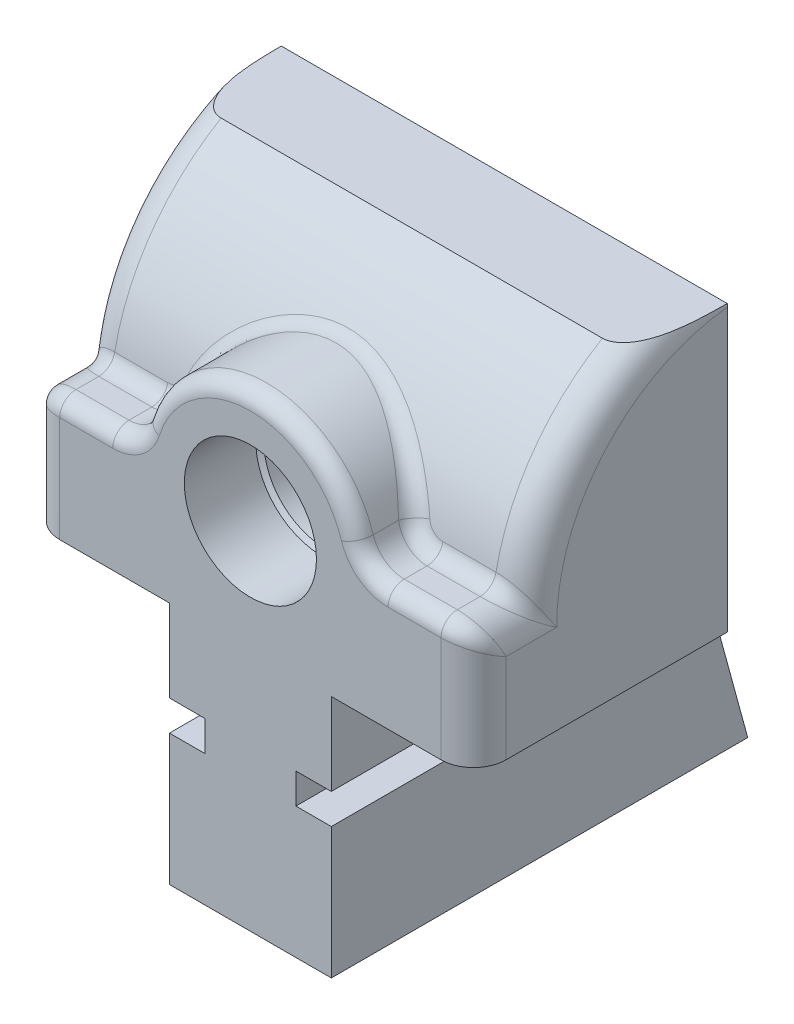
SolidWorks part; units mm, degrees
ref_plane "Front Plane" through (0, 0, 0) normal (0, 0, 1) x (1, 0, 0)
ref_plane "Top Plane" through (0, 0, 0) normal (0, 1, 0) x (1, 0, 0)
ref_plane "Right Plane" through (0, 0, 0) normal (1, 0, 0) x (0, 0, -1)
sketch "Sketch1" plane through (0, 0, 0) normal (0, 0, 1) x (1, 0, 0)
  line L0 (0, 66.9524) -> (0, 0) construction
  line L1 (12.6492, 0.0311) -> (12.6492, 38.1311)
  line L2 (12.6492, 38.1311) -> (34.8742, 38.1311)
  line L3 (34.8742, 38.1311) -> (34.8742, 57.1811)
  line L4 (-34.8742, 38.1311) -> (-34.8742, 57.1811)
  line L5 (-12.6492, 38.1311) -> (-34.8742, 38.1311)
  line L6 (-12.6492, 0.0311) -> (-12.6492, 38.1311)
  line L7 (-34.8742, 57.1811) -> (34.8742, 57.1811)
  line L8 (-12.6492, 0.0311) -> (12.6492, 0.0311)
  dimension "D1" = 38.1
  dimension "D2" = 22.225
  dimension "D3" = 19.05
  dimension "D4" = 25.2984
extrude "Boss-Extrude1" add sketch "Sketch1" along normal blind 65.0748
sketch "Sketch2" plane through (-34.8742, 0, 0) normal (-1, 0, 0) x (0, 0, 1)
  line L0 (56.8255, 57.1811) -> (25.4, 57.1811)
  line L1 (65.0748, 57.1811) -> (0, 57.1811) construction
  line L2 (25.4, 57.1811) -> (25.4, 82.5811)
  line L3 (25.4, 82.5811) -> (39.853, 82.5811)
  line L4 (65.0748, 57.1811) -> (65.0748, 38.1311) construction
  line L5 (65.0748, 38.1311) -> (0, 38.1311) construction
  arc A0 (39.853, 82.5811) -> (56.8255, 57.1811) centre (22.225, 52.4313) cw
  dimension "D2" = 34.925
  dimension "D4" = 3.175
  dimension "D1" = 39.6748
  dimension "D3" = 44.45
  dimension "D5" = 30.1498
extrude "Boss-Extrude2" add sketch "Sketch2" against normal up to surface (69.7484 mm away) up to face at (34.8742, 47.6561, 32.5374)
sketch "Sketch3" plane through (-34.8742, 0, 0) normal (-1, 0, 0) x (0, 0, 1)
  line L0 (25.4, 57.1811) -> (25.4, 34.9561)
  line L1 (25.4, 34.9561) -> (9.525, 34.9561)
  line L2 (9.525, 34.9561) -> (0, 0.0311)
  line L3 (0, 38.1311) -> (0, 0.0311) construction
  line L4 (65.0748, 0.0311) -> (0, 0.0311) construction
  dimension "D1" = 9.525
  dimension "D2" = 34.925
extrude "Cut-Extrude2" cut sketch "Sketch3" against normal through all and the other way through all flip side to cut
sketch "Sketch4" plane through (0, 0, 65.0748) normal (0, 0, 1) x (1, 0, 0)
  line L0 (0, 0) -> (0, 55.5498) construction
  line L1 (-17.4498, 55.5498) -> (17.4498, 55.5498)
  arc A0 (17.4498, 55.5498) -> (-17.4498, 55.5498) centre (0, 55.5498) ccw
  dimension "D2" = 34.8996
  dimension "D1" = 55.5498
extrude "Boss-Extrude3" add sketch "Sketch4" against normal up to surface (8.0643 mm away) up to face at (0, 70.8582, 49.8014)
sketch "Sketch5" plane through (0, 0, 65.0748) normal (0, 0, 1) x (1, 0, 0)
  circle A1 centre (0, 55.5498) radius 9.525
  dimension "D1" = 19.05
extrude "Cut-Extrude3" cut sketch "Sketch5" against normal blind 30.1498
hole_wizard "1-1/8-7 Tapped Hole1" positions "Sketch6" profile "Sketch7" tap size "1-1/8-7" standard "ANSI Inch"
sketch "Sketch6" plane through (0, 0, 65.0748) normal (0, 0, 1) x (1, 0, 0)
  point P0 (0, 55.5498)
sketch "Sketch7" plane through (0, 55.5498, 65.0748) normal (1, 0, 0) x (0, -1, 0)
  line L0 (0, 0) -> (0, 17.3799)
  line L1 (0, 17.3799) -> (10.3251, 11.176)
  line L2 (10.3251, 11.176) -> (10.3251, 0)
  line L5 (10.3251, 0) -> (0, 0)
  line L10 (0, 17.3799) -> (-10.3251, 11.176) construction
  line L11 (0, -6.35) -> (0, 107.95) construction
  dimension "Tap Drill Dia." = 20.6502
  dimension "Tap Drill Depth" = 11.176
  dimension "Drill Angle" = 118
cosmetic thread "Hole Thread1" parameters "D1"=57.15, "D2"=28.575
sketch "Sketch8" plane through (0, 0, 65.0748) normal (0, 0, 1) x (1, 0, 0)
  line L0 (0, 0) -> (0, 50.9626) construction
  line L1 (12.6492, 0.0311) -> (12.6492, 38.1311) construction
  line L2 (12.6492, 25.2787) -> (7.112, 25.2787)
  line L3 (12.6492, 25.2787) -> (12.6492, 20.5289)
  line L4 (12.6492, 20.5289) -> (7.112, 20.5289)
  line L5 (7.112, 25.2787) -> (7.112, 20.5289)
  line L6 (12.6492, 38.1311) -> (34.8742, 38.1311) construction
  dimension "D1" = 5.5372
  dimension "D2" = 4.7498
  dimension "D3" = 12.8524
extrude "Cut-Extrude4" cut sketch "Sketch8" against normal through all
mirror "Mirror1" about plane through (0, 0, 0) normal (1, 0, 0) of "Cut-Extrude4"
hole_wizard "1/4-20 Tapped Hole1" positions "Sketch9" profile "Sketch10" tap size "1/4-20" standard "ANSI Inch"
sketch "Sketch9" plane through (0, 0, 25.4) normal (0, 0, -1) x (-1, 0, 0)
  line L0 (0, 82.5811) -> (0, 25.8742) construction
  line L1 (-34.8742, 82.5811) -> (34.8742, 82.5811) construction
  line L2 (34.8742, 38.1311) -> (12.6492, 38.1311) construction
  point P0 (-19.05, 63.5311)
  point P8 (19.05, 63.5311)
  dimension "D1" = 38.1
  dimension "D2" = 25.4
sketch "Sketch10" plane through (19.05, 63.5311, 25.4) normal (1, 0, 0) x (0, 1, 0)
  line L0 (0, 0) -> (0, 17.5358)
  line L1 (0, 17.5358) -> (2.5527, 16.002)
  line L2 (2.5527, 16.002) -> (2.5527, 0)
  line L5 (2.5527, 0) -> (0, 0)
  line L10 (0, 17.5358) -> (-2.5527, 16.002) construction
  line L11 (0, -6.35) -> (0, 107.95) construction
  dimension "Tap Drill Dia." = 5.1054
  dimension "Tap Drill Depth" = 16.002
  dimension "Drill Angle" = 118
cosmetic thread "Hole Thread2" parameters "D1"=12.7, "D2"=6.35
cosmetic thread "Hole Thread3" parameters "D1"=12.7, "D2"=6.35
fillet "Fillet1" radius 5.08 8 edges at (34.8742, 71.8353, 51.2637) (34.8742, 57.1811, 60.9502) (34.8742, 47.6561, 65.0748) (-34.8742, 71.8353, 51.2637) (-34.8742, 47.6561, 65.0748) (-34.8742, 57.1811, 60.9502) (17.3734, 57.1811, 60.9502) (-17.3734, 57.1811, 60.9502)
fillet "Fillet2" radius 2.54 14 edges at (33.3863, 55.6932, 63.5869) (25.6506, 57.1811, 65.0748) (18.4971, 58.1688, 65.0748) (0, 72.9996, 65.0748) (-18.4971, 58.1688, 65.0748) (-33.3863, 55.6932, 63.5869) (32.3808, 56.4733, 56.2026) (25.6506, 57.1811, 56.8255) (18.656, 58.0566, 56.694) (-2.1278, 72.8694, 50.5453) (-18.3625, 58.2713, 56.6583) (-32.3808, 56.4733, 56.2026) (-25.6506, 57.1811, 65.0748) (-25.6506, 57.1811, 56.8255)
hole_wizard "#25 (0.1495) Diameter Hole1" positions "Sketch11" profile "Sketch12" hole size "#25" standard "ANSI Inch"
sketch "Sketch11" plane through (0, 0.0311, 0) normal (0, -1, 0) x (-1, 0, 0)
  line L0 (0, 0) -> (0, -65.0748) construction
  line L1 (12.6492, -65.0748) -> (-12.6492, -65.0748) construction
  point P0 (-7.9375, -34.925)
  dimension "D1" = 30.1498
  dimension "D2" = 7.9375
sketch "Sketch12" plane through (7.9375, 0.0311, 34.925) normal (1, 0, 0) x (0, 0, -1)
  line L0 (0, 0) -> (0, 28.1156)
  line L1 (0, 28.1156) -> (1.8986, 26.9748)
  line L2 (1.8986, 26.9748) -> (1.8986, 0)
  line L5 (1.8986, 0) -> (0, 0)
  line L10 (0, 28.1156) -> (-1.8987, 26.9748) construction
  line L11 (0, -6.35) -> (0, 107.95) construction
  dimension "Hole Dia." = 3.7973
  dimension "Hole Depth" = 26.9748
  dimension "Drill Angle" = 118
hole_wizard "1/4-28 Tapped Hole2" positions "Sketch15" profile "Sketch16" tap size "1/4-28" standard "ANSI Inch"
sketch "Sketch15" plane through (0, 0.0311, 0) normal (0, -1, 0) x (-1, 0, 0)
  point P0 (-7.9375, -34.925)
sketch "Sketch16" plane through (7.9375, 0.0311, 34.925) normal (1, 0, 0) x (0, 0, -1)
  line L0 (0, 0) -> (0, 20.6754)
  line L1 (0, 20.6754) -> (2.7051, 19.05)
  line L2 (2.7051, 19.05) -> (2.7051, 0)
  line L5 (2.7051, 0) -> (0, 0)
  line L10 (0, 20.6754) -> (-2.7051, 19.05) construction
  line L11 (0, -6.35) -> (0, 107.95) construction
  dimension "Tap Drill Dia." = 5.4102
  dimension "Tap Drill Depth" = 19.05
  dimension "Drill Angle" = 118
cosmetic thread "Hole Thread5" parameters "D1"=12.7, "D2"=6.35
hole_wizard "7/32 (0.21875) Diameter Hole2" positions "Sketch19" profile "Sketch20" hole size "7/32" standard "ANSI Inch"
sketch "Sketch19" plane through (0, 0.0311, 0) normal (0, -1, 0) x (-1, 0, 0)
  point P0 (-7.9375, -34.925)
sketch "Sketch20" plane through (7.9375, 0.0311, 34.925) normal (1, 0, 0) x (0, 0, -1)
  line L0 (0, 0) -> (0, 11.1943)
  line L1 (0, 11.1943) -> (2.7781, 9.525)
  line L2 (2.7781, 9.525) -> (2.7781, 0)
  line L5 (2.7781, 0) -> (0, 0)
  line L10 (0, 11.1943) -> (-2.7781, 9.525) construction
  line L11 (0, -6.35) -> (0, 107.95) construction
  dimension "Hole Dia." = 5.5562
  dimension "Hole Depth" = 9.525
  dimension "Drill Angle" = 118
mirror "Mirror2" about plane through (0, 0, 0) normal (1, 0, 0) of "1/4-28 Tapped Hole2", "7/32 (0.21875) Diameter Hole2", "#25 (0.1495) Diameter Hole1"
cosmetic thread "Hole Thread6" parameters "D1"=12.7, "D2"=6.35
